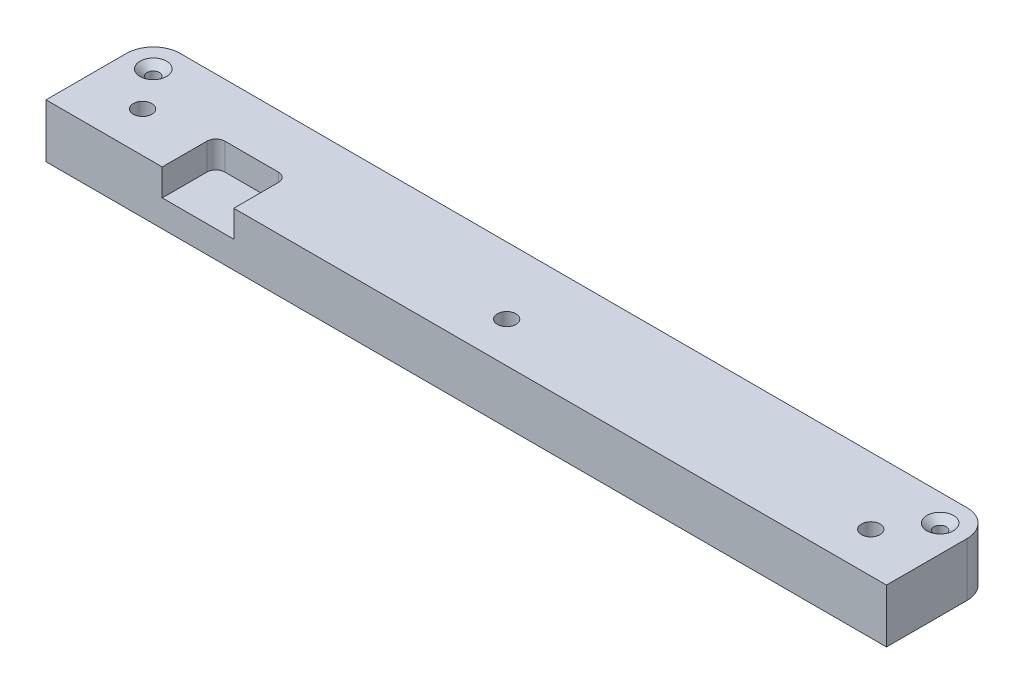
SolidWorks part; units mm, degrees
ref_plane "Front Plane" through (0, 0, 0) normal (0, 0, 1) x (1, 0, 0)
ref_plane "Top Plane" through (0, 0, 0) normal (0, 1, 0) x (1, 0, 0)
ref_plane "Right Plane" through (0, 0, 0) normal (1, 0, 0) x (0, 0, -1)
sketch "Sketch1" plane through (0, 0, 0) normal (0, 1, 0) x (1, 0, 0)
  line L1 (0, 0) -> (298.45, 0)
  line L2 (0, 0) -> (0, 38.1)
  line L3 (0, 38.1) -> (298.45, 38.1)
  line L4 (298.45, 0) -> (298.45, 38.1)
  dimension "D1" = 38.1
  dimension "D2" = 298.45
extrude "Boss-Extrude1" add sketch "Sketch1" along normal blind 19.05
fillet "Fillet1" radius 9.525 2 edges at (298.45, 9.525, -38.1) (0, 9.525, -38.1)
sketch "Sketch2" plane through (0, 19.05, 0) normal (0, 1, 0) x (1, 0, 0)
  line L0 (0, 14.351) -> (298.45, 14.351) construction
  line L1 (0, 28.575) -> (0, 0) construction
  line L2 (298.45, 0) -> (298.45, 28.575) construction
  line L3 (288.925, 38.1) -> (9.525, 38.1) construction
  circle A0 centre (19.939, 14.351) radius 3.302
  circle A1 centre (149.225, 14.351) radius 3.302
  circle A2 centre (278.511, 14.351) radius 3.302
  dimension "D2" = 6.604
  dimension "D1" = 23.749
  dimension "D3" = 19.939
  dimension "D4" = 19.939
extrude "Cut-Extrude1" cut sketch "Sketch2" against normal blind 14.2875
sketch "Sketch4" plane through (0, 0, 0) normal (0, -1, 0) x (1, 0, 0)
  circle A0 centre (19.939, -14.351) radius 1.6256
  circle A1 centre (149.225, -14.351) radius 1.6256
  circle A2 centre (278.511, -14.351) radius 1.6256
  dimension "D1" = 3.2512
extrude "Cut-Extrude2" cut sketch "Sketch4" against normal through all
sketch "Sketch5" plane through (0, 0, 0) normal (0, -1, 0) x (1, 0, 0)
  circle A0 centre (19.939, -14.351) radius 2.667
  circle A1 centre (149.225, -14.351) radius 2.667
  circle A2 centre (278.511, -14.351) radius 2.667
  dimension "D1" = 5.334
extrude "Cut-Extrude3" cut sketch "Sketch5" against normal blind 2.921
sketch "Sketch6" plane through (0, 19.05, 0) normal (0, 1, 0) x (1, 0, 0)
  line L0 (298.45, 28.575) -> (0, 28.575) construction
  line L1 (0, 28.575) -> (0, 0) construction
  line L2 (298.45, 0) -> (298.45, 28.575) construction
  circle A0 centre (9.525, 28.575) radius 2.1844
  circle A1 centre (288.925, 28.575) radius 2.1844
  dimension "D3" = 4.3688
  dimension "D1" = 9.525
  dimension "D2" = 9.525
extrude "Cut-Extrude4" cut sketch "Sketch6" against normal through all contours L0 A1 | A1 L0 | A0 region at (288.925, 19.05, -27.6479) region at (288.925, 19.05, -29.5021)
chamfer "Chamfer1" distance 2.54 angle 41 2 edges at (288.925, 19.05, -26.3906) (9.525, 19.05, -26.3906) first distance on face at (9.525, 19.05, -26.3906)
sketch "Sketch7" plane through (0, 19.05, 0) normal (0, 1, 0) x (1, 0, 0)
  line L0 (288.925, 38.1) -> (9.525, 38.1) construction
  circle A0 centre (149.225, 28.575) radius 7.239
  dimension "D2" = 14.478
  dimension "D1" = 9.525
extrude "Cut-Extrude5" cut sketch "Sketch7" against normal through all from offset 5.08 offset against normal yes
sketch "Sketch8" plane through (0, 0, 0) normal (0, -1, 0) x (1, 0, 0)
  line L0 (0, 0) -> (298.45, 0) construction
  line L1 (41.275, 0) -> (66.675, 0)
  line L2 (41.275, 0) -> (41.275, -19.05)
  line L3 (41.275, -19.05) -> (66.675, -19.05)
  line L4 (66.675, 0) -> (66.675, -19.05)
  line L5 (0, -28.575) -> (0, 0) construction
  dimension "D1" = 41.275
  dimension "D2" = 25.4
  dimension "D3" = 19.05
extrude "Cut-Extrude6" cut sketch "Sketch8" against normal blind 9.525 from offset 9.525 offset against normal yes
fillet "Fillet2" radius 3.175 2 edges at (66.675, 14.2875, -19.05) (41.275, 14.2875, -19.05)
